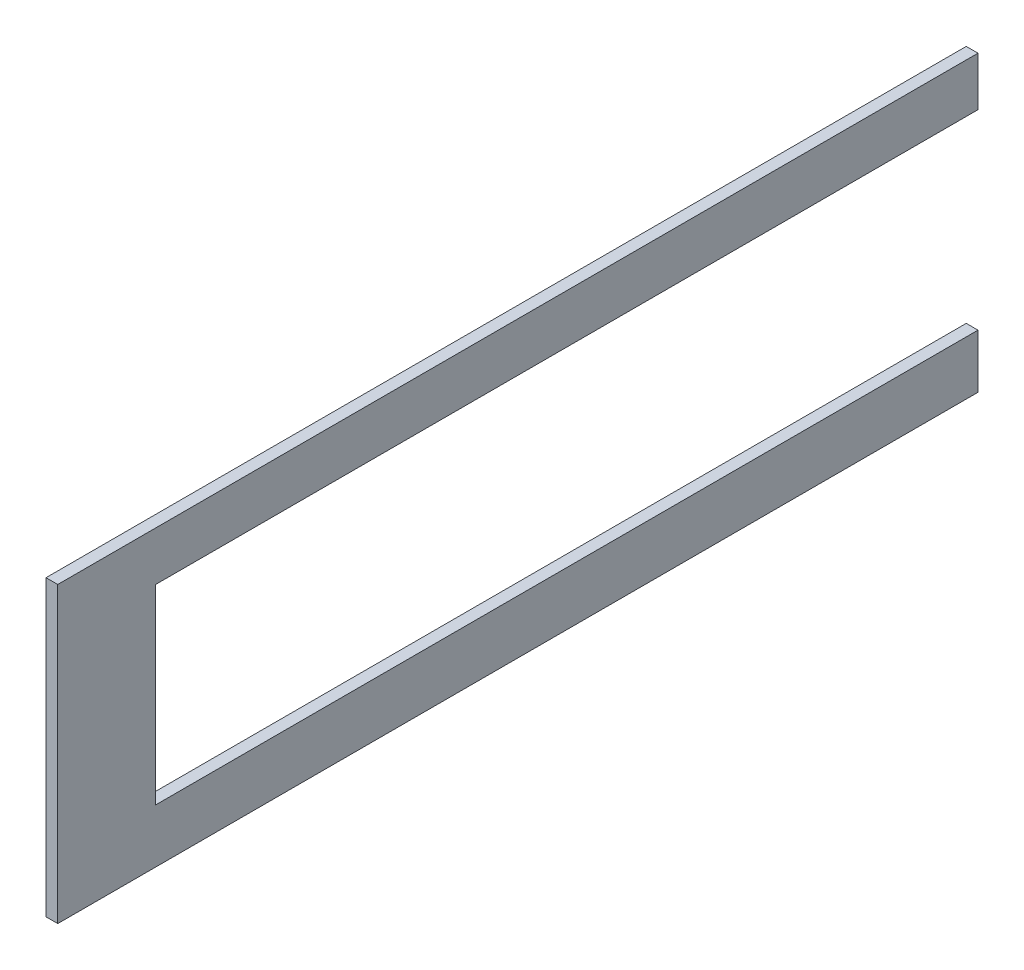
SolidWorks part; units mm, degrees
ref_plane "Front" through (0, 0, 0) normal (0, 0, 1) x (1, 0, 0)
ref_plane "Top" through (0, 0, 0) normal (0, 1, 0) x (1, 0, 0)
ref_plane "Right" through (0, 0, 0) normal (1, 0, 0) x (0, 0, -1)
sketch "Sketch1" plane through (0, 0, 0) normal (1, 0, 0) x (0, 0, -1)
  line L0 (470, 125) -> (470, 150)
  line L1 (0, 0) -> (470, 0)
  line L2 (0, 0) -> (0, 150)
  line L3 (0, 150) -> (470, 150)
  line L4 (470, 0) -> (470, 27.5)
  line L5 (470, 125) -> (50, 125)
  line L7 (470, 27.5) -> (50, 27.5)
  line L8 (50, 125) -> (50, 27.5)
  dimension "D1" = 420
  dimension "D2" = 150
  dimension "D3" = 27.5
  dimension "D4" = 25
  dimension "D5" = 50
extrude "Boss-Extrude1" add sketch "Sketch1" along normal blind 6
